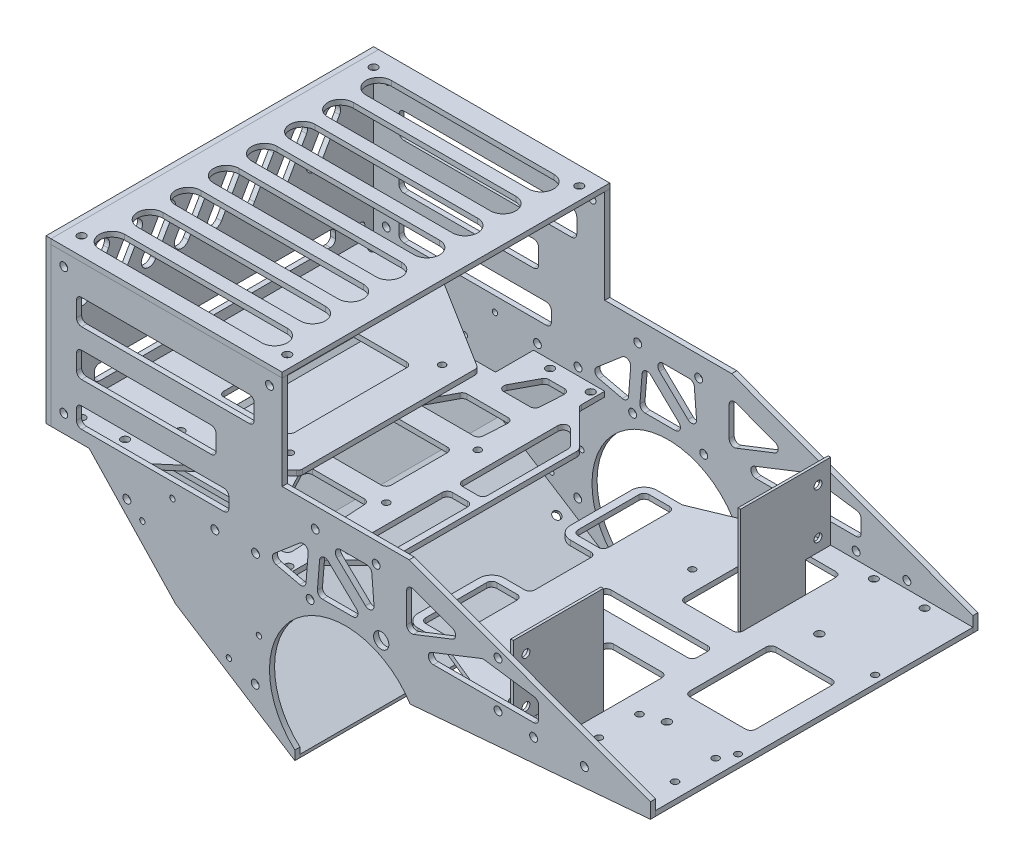
SolidWorks part; units mm, degrees
material "Thornel Mat VMA"
ref_plane "前视基准面" through (0, 0, 0) normal (0, 0, 1) x (1, 0, 0)
ref_plane "上视基准面" through (0, 0, 0) normal (0, 1, 0) x (1, 0, 0)
ref_plane "右视基准面" through (0, 0, 0) normal (1, 0, 0) x (0, 0, -1)
sketch "草图1" plane through (0, 0, 0) normal (0, 0, 1) x (1, 0, 0)
  line L1 (-45, 65) -> (25, 65)
  line L2 (25, 65) -> (120, 30)
  line L3 (120, 30) -> (120, 24)
  line L4 (120, 24) -> (41.8272, 24) construction
  line L5 (0, 32) -> (0, 57) construction
  line L6 (-12, 57) -> (12, 57) construction
  line L9 (29.8272, 3.2154) -> (41.8272, 24) construction
  line L15 (-18, 24) -> (-45, 24)
  line L17 (-45, 24) -> (-45, 65)
  line L18 (-14, 32) -> (14, 32) construction
  line L19 (60, 49) -> (90.2493, 37.8555) construction
  line L22 (120, 24) -> (120, 16) construction
  line L23 (120, 16) -> (25.3772, 16) construction
  line L24 (120, 24) -> (25.3772, 16)
  circle A2 centre (-12, 57) radius 1.55
  circle A3 centre (12, 57) radius 1.55
  circle A10 centre (90.2493, 37.8555) radius 1.55 construction
  circle A11 centre (60, 49) radius 1.55
  circle A13 centre (14, 32) radius 1.55
  circle A14 centre (-14, 32) radius 1.55
  arc A15 (-18, 24) -> (25.3772, 16) centre (0, 0) cw
  arc A16 (25.3772, 16) -> (29.8272, 3.2154) centre (0, 0) cw construction
  circle A17 centre (60, 31) radius 1.55
  point P27 (0, 57)
  dimension "D3" = 28
  dimension "D5" = 7
  dimension "D11" = 30
  dimension "D12" = 3.1
  dimension "D13" = 60
  dimension "D15" = 8
  dimension "D18" = 60
  dimension "D19" = 3.1
  dimension "D1" = 24
  dimension "D4" = 24
  dimension "D6" = 120
  dimension "D7" = 70
  dimension "D8" = 6
  dimension "D9" = 8
  dimension "D10" = 25
  dimension "D14" = 12
  dimension "D16" = 57
  dimension "D17" = 25
  dimension "D20" = 32
  dimension "D21" = 60
extrude "凸台-拉伸1" add sketch "草图1" along normal blind 2
sketch "草图2" plane through (0, 24, 0) normal (0, 1, 0) x (1, 0, 0)
  line L0 (120, -2) -> (120, 0) construction
  line L4 (120, 0) -> (120, 125)
  line L5 (120, 0) -> (21, 0)
  line L7 (45, 89.5) -> (117, 89.5) construction
  line L8 (45, 89.5) -> (45, 35.5) construction
  line L9 (45, 35.5) -> (117, 35.5) construction
  line L11 (45, 89.5) -> (117, 35.5) construction
  line L12 (45, 35.5) -> (117, 89.5) construction
  line L16 (120, 0) -> (25, 0) construction
  line L17 (21, 0) -> (21, 125) construction
  line L18 (21, 125) -> (120, 125)
  line L20 (117, 35.5) -> (117, 89.5) construction
  line L25 (84, 13.7) -> (114, 13.7) construction
  line L26 (84, 13.7) -> (84, 29.7) construction
  line L27 (84, 29.7) -> (114, 29.7) construction
  line L28 (114, 13.7) -> (114, 29.7) construction
  line L33 (81, 62.5) -> (76, 62.5) construction
  line L35 (21, 125) -> (21, 109.5)
  line L36 (21, 109.5) -> (11, 109.5)
  line L41 (6, 104.5) -> (6, 80.5)
  line L42 (11, 75.5) -> (21, 75.5)
  line L43 (21, 106.5) -> (11, 106.5)
  line L44 (9, 104.5) -> (9, 80.5)
  line L45 (11, 78.5) -> (21, 78.5)
  line L46 (21, 78.5) -> (21, 106.5)
  line L48 (21, 46.5) -> (21, 18.5)
  line L49 (21, 15.5) -> (11, 15.5)
  line L52 (21, 18.5) -> (11, 18.5)
  line L53 (34, 66.5) -> (76, 66.5)
  line L54 (34, 66.5) -> (34, 58.5)
  line L55 (34, 58.5) -> (76, 58.5)
  line L56 (76, 66.5) -> (76, 58.5)
  line L57 (6, 20.5) -> (6, 44.5)
  line L58 (9, 20.5) -> (9, 44.5)
  line L59 (11, 46.5) -> (21, 46.5)
  line L60 (11, 49.5) -> (21, 49.5)
  line L61 (21, 49.5) -> (21, 75.5)
  line L62 (21, 15.5) -> (21, 0)
  line L63 (92, 32.5) -> (92, 92.5) construction
  line L64 (120, 62.5) -> (21, 62.5) construction
  circle A0 centre (117, 89.5) radius 1.3
  circle A1 centre (117, 35.5) radius 1.3
  circle A2 centre (45, 35.5) radius 1.3
  circle A3 centre (45, 89.5) radius 1.3
  circle A7 centre (84, 13.7) radius 1.35
  circle A8 centre (84, 29.7) radius 1.35
  circle A9 centre (114, 13.7) radius 1.35
  circle A10 centre (114, 29.7) radius 1.35
  arc A11 (6, 80.5) -> (11, 75.5) centre (11, 80.5) ccw
  arc A12 (11, 109.5) -> (6, 104.5) centre (11, 104.5) ccw
  arc A13 (11, 106.5) -> (9, 104.5) centre (11, 104.5) ccw
  arc A14 (9, 80.5) -> (11, 78.5) centre (11, 80.5) ccw
  arc A15 (11, 15.5) -> (6, 20.5) centre (11, 20.5) cw
  arc A16 (11, 18.5) -> (9, 20.5) centre (11, 20.5) cw
  arc A17 (9, 44.5) -> (11, 46.5) centre (11, 44.5) cw
  arc A18 (6, 44.5) -> (11, 49.5) centre (11, 44.5) cw
  circle A19 centre (92, 92.5) radius 1.6
  circle A20 centre (92, 32.5) radius 1.6
  circle A21 centre (60, 5) radius 1.6
  circle A22 centre (60, 120) radius 1.6
  point P9 (81, 62.5)
  dimension "D4" = 2.6
  dimension "D10" = 30
  dimension "D15" = 28
  dimension "D17" = 5
  dimension "D19" = 42
  dimension "D20" = 12
  dimension "D21" = 28
  dimension "D22" = 3.2
  dimension "D23" = 3
  dimension "D24" = 3
  dimension "D8" = 2.7
  dimension "D13" = 5
  dimension "D25" = 5
  dimension "D2" = 54
  dimension "D3" = 72
  dimension "D5" = 24
  dimension "D6" = 3
  dimension "D7" = 0
  dimension "D9" = 16
  dimension "D11" = 5.8
  dimension "D12" = 6
  dimension "D14" = 3
  dimension "D16" = 13
  dimension "D18" = 8
  dimension "108" = 125
  dimension "D26" = 60
extrude "凸台-拉伸2" add sketch "草图2" along normal blind 2 separate body
extrude "凸台-拉伸3" add sketch "草图1<2>" against normal blind 2 from surface separate body starting at face at (70.5, 25, -125)
sketch "草图1<2>" plane through (0, 0, 0) normal (0, 0, 1) x (1, 0, 0) same geometry as "草图1"
sketch "草图16" plane through (0, 65, 0) normal (0, 1, 0) x (1, 0, 0)
  line L0 (-50, 30) -> (-85, 0)
  line L1 (-90, 125) -> (-116, 125)
  line L2 (-50, 100) -> (-50, 30)
  line L3 (-85, 0) -> (-116, 0)
  line L4 (-116, 125) -> (-116, 0)
  line L5 (-58, 94) -> (-98, 94) construction
  line L6 (-58, 94) -> (-58, 34) construction
  line L7 (-58, 34) -> (-98, 34) construction
  line L8 (-98, 94) -> (-98, 34) construction
  line L9 (-58, 94) -> (-98, 34) construction
  line L10 (-58, 34) -> (-98, 94) construction
  line L11 (25, 125) -> (-45, 125) construction
  line L12 (-50, 100) -> (-90, 125)
  line L13 (25, 0) -> (-45, 0) construction
  line L14 (-92, 88) -> (-92, 40)
  line L15 (-64, 40) -> (-92, 40)
  line L16 (-64, 88) -> (-64, 40)
  line L17 (-64, 88) -> (-92, 88)
  circle A0 centre (-98, 34) radius 1.35
  circle A1 centre (-58, 34) radius 1.35
  circle A2 centre (-58, 94) radius 1.35
  circle A3 centre (-98, 94) radius 1.35
  circle A4 centre (-111, 120) radius 1.55
  circle A5 centre (-111, 5) radius 1.55
  point P4 (-78, 64)
  dimension "D1" = 2.7
  dimension "D12" = 3.1
  dimension "D2" = 60
  dimension "D3" = 40
  dimension "D4" = 78
  dimension "D5" = 64
  dimension "D6" = 8
  dimension "D7" = 18
  dimension "D8" = 25
  dimension "D9" = 35
  dimension "D10" = 30
  dimension "D11" = 40
  dimension "D13" = 5
  dimension "D14" = 5
  dimension "D15" = 5
  dimension "D16" = 5
  dimension "D17" = 6
extrude "凸台-拉伸13" add sketch "草图16" along normal blind 2 from offset 25 separate body offset against normal yes
sketch "草图17" plane through (0, 24, 0) normal (0, -1, 0) x (1, 0, 0)
  line L0 (-45, -125) -> (-18, -125) construction
  line L1 (-66, -80) -> (-30, -80) construction
  line L2 (-66, -80) -> (-66, -44) construction
  line L3 (-66, -44) -> (-30, -44) construction
  line L4 (-30, -80) -> (-30, -44) construction
  line L5 (-25, -125) -> (-53, -125)
  line L6 (-25, -125) -> (-25, 0)
  line L7 (-25, 0) -> (-53, 0)
  line L8 (-90, -110) -> (-90, -15)
  line L10 (-45, 0) -> (-18, 0) construction
  line L11 (-25, -62.5) -> (-90, -62.5) construction
  line L13 (-53, 0) -> (-53, -15)
  line L14 (-53, -15) -> (-90, -15)
  line L15 (-53, -125) -> (-53, -110)
  line L16 (-53, -110) -> (-90, -110)
  line L17 (-53, -3) -> (-25, -3) construction
  line L18 (-61, -75) -> (-35, -75)
  line L19 (-35, -75) -> (-35, -49)
  line L20 (-61, -49) -> (-35, -49)
  line L21 (-61, -75) -> (-61, -49)
  line L22 (-43.5, -122) -> (-54.75, -101) construction
  line L25 (-54.75, -101) -> (-66, -80) construction
  line L26 (-43.5, -122) -> (-27.5, -122) construction
  line L27 (-54.75, -101) -> (-28.75, -101) construction
  line L28 (-27.5, -122) -> (-28.75, -101) construction
  line L29 (-28.75, -101) -> (-30, -80) construction
  line L30 (-41.105, -118) -> (-48.0693, -105)
  line L31 (-48.0693, -105) -> (-32.519, -105)
  line L32 (-31.7452, -118) -> (-32.519, -105)
  line L33 (-41.105, -118) -> (-31.7452, -118)
  line L34 (-52.355, -97) -> (-59.3193, -84)
  line L35 (-59.3193, -84) -> (-33.769, -84)
  line L36 (-32.9952, -97) -> (-33.769, -84)
  line L37 (-52.355, -97) -> (-32.9952, -97)
  line L38 (-52.355, -28) -> (-32.9952, -28)
  line L39 (-32.9952, -28) -> (-33.769, -41)
  line L40 (-59.3193, -41) -> (-33.769, -41)
  line L41 (-52.355, -28) -> (-59.3193, -41)
  line L42 (-41.105, -7) -> (-31.7452, -7)
  line L43 (-31.7452, -7) -> (-32.519, -20)
  line L44 (-48.0693, -20) -> (-32.519, -20)
  line L45 (-41.105, -7) -> (-48.0693, -20)
  circle A0 centre (-66, -80) radius 1.35
  circle A1 centre (-30, -80) radius 1.35
  circle A2 centre (-30, -44) radius 1.35
  circle A3 centre (-66, -44) radius 1.35
  circle A4 centre (-27.5, -3) radius 1.55
  circle A5 centre (-43.5, -3) radius 1.55
  circle A6 centre (-27.5, -122) radius 1.55
  circle A7 centre (-43.5, -122) radius 1.55
  dimension "D1" = 2.7
  dimension "D4" = 37
  dimension "D10" = 3.1
  dimension "D14" = 4
  dimension "D2" = 36
  dimension "D3" = 30
  dimension "D5" = 90
  dimension "D6" = 25
  dimension "D7" = 45
  dimension "D8" = 15
  dimension "D9" = 3
  dimension "D11" = 16
  dimension "D12" = 2.5
  dimension "D13" = 5
  dimension "D15" = 4
extrude "凸台-拉伸14" add sketch "草图17" along normal blind 2 from offset 10 separate body offset against normal yes
sketch "草图47" plane through (0, 34, 0) normal (0, 1, 0) x (1, 0, 0)
  line L0 (-25, 115) -> (-10, 100)
  line L1 (-10, 100) -> (-10, 25)
  line L2 (-10, 25) -> (-25, 10)
  line L3 (-25, 125) -> (-25, 0) construction
  line L4 (-25, 62.5) -> (-5.2813, 62.5) construction
  line L10 (-22.5, 108.9645) -> (-22.5, 16.0355)
  line L11 (-12.5, 26.0355) -> (-22.5, 16.0355)
  line L12 (-12.5, 98.9645) -> (-12.5, 26.0355)
  line L13 (-22.5, 108.9645) -> (-12.5, 98.9645)
  line L14 (-12.5, 84.5) -> (-22.5, 84.5) construction
  line L15 (-12.5, 80.5) -> (-22.5, 80.5) construction
  line L16 (-12.5, 60.5) -> (-22.5, 60.5)
  line L17 (-12.5, 64.5) -> (-22.5, 64.5)
  line L18 (-12.5, 44.5) -> (-22.5, 44.5) construction
  line L19 (-12.5, 40.5) -> (-22.5, 40.5) construction
  line L20 (-25, 115) -> (-25, 10) construction
  line L21 (-25, 115) -> (-25, 10)
  line L22 (-53, 125) -> (-25, 125) construction
  line M15 (-25, 0) -> (-25, 125)
  dimension "D1" = 15
  dimension "D2" = 45
  dimension "D3" = 2
  dimension "D5" = 4
  dimension "D6" = 18
  dimension "D7" = 10
  dimension "D4" = 2.5
extrude "凸台-拉伸27" add sketch "草图47" against normal up to surface (2 mm away) contours L12 L17 L10 L16 | L2 L1 L0 L10 L13 L12 L11 M15 region at (-18.25, 34, -106.75) region at (-17.5, 34, -62.5) up to face at (-29.05, 32, -122)
sketch "草图18" plane through (0, 0, -127) normal (0, 0, -1) x (-1, 0, 0)
  line L0 (45, 40) -> (101, 40) construction
  line L1 (45, 65) -> (45, 24) construction
  line L2 (101, 40) -> (67, 4)
  line L3 (67, 4) -> (20, -26)
  line L4 (20, -26) -> (20, -22.3607)
  line L5 (45, 24) -> (18, 24) construction
  line L6 (45, 40) -> (45, 24)
  line L7 (45, 24) -> (18, 24)
  line L8 (90, 42) -> (116, 42) construction
  line L13 (116, 40) -> (25, 40) construction
  line L14 (116, 40) -> (116, 102)
  line L15 (116, 102) -> (25, 102)
  line L16 (25, 40) -> (25, 102) construction
  line L17 (90, 40) -> (116, 40) construction
  line L18 (25, 102) -> (25, 65)
  line L19 (25, 65) -> (45, 65)
  line L20 (-25, 65) -> (45, 65) construction
  line L21 (45, 65) -> (45, 40)
  line L22 (101, 40) -> (116, 40)
  arc A0 (18, 24) -> (20, -22.3607) centre (0, 0) cw
  arc A1 (18, 24) -> (-25.3772, 16) centre (0, 0) ccw construction
  dimension "D1" = 56
  dimension "D2" = 22
  dimension "D3" = 91
  dimension "D4" = 50
  dimension "D5" = 25
  dimension "D6" = 36
  dimension "D7" = 60
  dimension "D8" = 25
extrude "凸台-拉伸15" add sketch "草图18" against normal up to surface (2 mm away) up to face at (61.55, 49, -125)
sketch "草图19" plane through (0, 0, -125) normal (0, 0, 1) x (1, 0, 0)
  line L0 (-20, -26) -> (-67, 4) construction
  line L1 (-67, 4) -> (-101, 40) construction
  line L2 (-20, -26) -> (-66.8959, 3.9335)
  line L3 (-67.0848, 4.0898) -> (-94.1338, 32.7299)
  line L4 (-19.462, -25.1571) -> (-66.3578, 4.7764)
  line L5 (-66.3578, 4.7764) -> (-93.4068, 33.4165)
  line L6 (-101, 40) -> (-100.273, 40.6866) construction
  line L7 (-20, -26) -> (-19.462, -25.1571)
  line L8 (-66.3578, 4.7764) -> (-67.0848, 4.0898)
  line L9 (-66.3578, 4.7764) -> (-66.8959, 3.9335)
  line L10 (-67, 4) -> (-101, 40) construction
  line L11 (-20, -26) -> (-67, 4) construction
  line L12 (-94.1338, 32.7299) -> (-93.4068, 33.4165)
  line L13 (-94.1338, 32.7299) -> (-101, 40) construction
  line L14 (-93.4068, 33.4165) -> (-100.273, 40.6866) construction
  line L15 (-66.3578, 4.7764) -> (-100.273, 40.6866) construction
  line M2 (-20, -26) -> (-20, -22.3607)
  line M11 (-101, 40) -> (-67, 4)
  line M12 (-67, 4) -> (-20, -26)
  dimension "D2" = 10
  dimension "D1" = 1
extrude "凸台-拉伸16" add sketch "草图19" along normal blind 125 separate body contours L8 L5 M11 | L4 L9 M12 M2 region at (-43.3137, -10.5269, -125) region at (-80.2458, 18.7532, -125)
sketch "草图38" plane through (0, 24, 0) normal (0, -1, 0) x (1, 0, 0)
  line L0 (104, -3) -> (84, -3) construction
  line L2 (120, 0) -> (120, -125) construction
  line L3 (42, -62.5) -> (120, -62.5) construction
  line L5 (120, 0) -> (25, 0) construction
  circle A0 centre (104, -3) radius 1.55
  circle A1 centre (84, -3) radius 1.55
  circle A2 centre (84, -122) radius 1.55
  circle A3 centre (104, -122) radius 1.55
  dimension "D2" = 3.1
  dimension "D1" = 20
  dimension "D3" = 3
  dimension "D4" = 16
extrude "切除-拉伸12" cut sketch "草图38" against normal up to surface (2 mm away) up to face at (55, 26, -62.5)
sketch "草图31" plane through (0, 0, -127) normal (0, 0, -1) x (-1, 0, 0)
  line L0 (39.3872, -13.6252) -> (35.621, -7.7247) construction
  line L1 (20, -24.8137) -> (66.3578, 4.7764) construction
  line L2 (88.3298, 28.0409) -> (86.1487, 30.1007) construction
  line L3 (66.3578, 4.7764) -> (93.4068, 33.4165) construction
  line L4 (66.3578, 4.7764) -> (67.0848, 4.0898) construction
  line L5 (20, -26) -> (67, 4) construction
  circle A0 centre (35.621, -7.7247) radius 1.55
  circle A1 centre (86.1487, 30.1007) radius 1.55
  dimension "D2" = 3.1
  dimension "D1" = 7
  dimension "D3" = 32
  dimension "D4" = 23
  dimension "D5" = 3
extrude "切除-拉伸7" cut sketch "草图31" against normal blind 2
sketch "草图62" plane through (-17.5812, -27.5439, 0) normal (-0.538, -0.8429, 0) x (0.8429, -0.538, 0)
  line L0 (-24.3195, -125) -> (-27.4195, -125) construction
  line L1 (-24.3195, -125) -> (-27.4195, -125) construction
  line L2 (-25.8695, -125) -> (-25.8695, -120) construction
  line L3 (-2.8695, -62.5) -> (-58.5044, -62.5) construction
  line L4 (-2.8695, 0) -> (-2.8695, -125) construction
  line L5 (-58.5044, 0) -> (-58.5044, -125) construction
  circle A0 centre (-25.8695, -120) radius 1.55
  circle A1 centre (-25.8695, -5) radius 1.55
  dimension "D1" = 5
  dimension "D2" = 3.1
extrude "切除-拉伸28" cut sketch "草图62" against normal through all
sketch "草图39" plane through (0, 0, -127) normal (0, 0, -1) x (-1, 0, 0)
  line L0 (-102.45, 26) -> (-105.55, 26) construction
  line L1 (-102.45, 26) -> (-105.55, 26) construction
  line L2 (-104, 26) -> (-104, 29) construction
  line L3 (-104, 29) -> (-74, 29) construction
  line L4 (-120, 26) -> (-21, 26) construction
  circle A0 centre (-74, 29) radius 1.55
  circle A1 centre (-94, 29) radius 1.55
  dimension "D1" = 20
  dimension "D3" = 3.1
  dimension "D2" = 10
  dimension "D4" = 3
extrude "切除-拉伸13" cut sketch "草图39" against normal through all
sketch "草图41" plane through (0, 0, 0) normal (0, 0, -1) x (-1, 0, 0)
  line L3 (-24, 56.8428) -> (-24, 39.3723)
  line L4 (-24, 34) -> (-76, 34)
  line L5 (-86.0018, 34) -> (-76, 37.6849) construction
  line L7 (-120, 30) -> (-25, 65) construction
  line L8 (-54, 45.7901) -> (-76, 42.6849)
  line L9 (-21, 26) -> (-120, 26) construction
  line L10 (-76, 42.6849) -> (-76, 37.6849)
  line L11 (-72.4303, 39) -> (-54, 45.7901) construction
  line L12 (-46.9445, 48.3895) -> (-24, 56.8428)
  line L13 (-76, 37.6849) -> (-72.4303, 39) construction
  line L14 (-24, 39.3723) -> (-46.9445, 48.3895)
  line L15 (-54, 45.7901) -> (-24, 34)
  line L16 (-54, 45.7901) -> (-46.9445, 48.3895) construction
  line L17 (-24, 39.3723) -> (-24, 34) construction
  line L18 (-76, 37.6849) -> (-76, 34)
  line L19 (-76, 34) -> (-86.0018, 34) construction
  circle A2 centre (-14, 32) radius 1.55 construction
  dimension "D2" = 30
  dimension "D5" = 8
  dimension "D6" = 10
  dimension "D7" = 8
  dimension "D8" = 5
  dimension "D9" = 5
  dimension "D10" = 22
extrude "切除-拉伸15" cut sketch "草图41" against normal through all both and the other way through all
sketch "草图48" plane through (0, 24, 0) normal (0, -1, 0) x (1, 0, 0)
  line L1 (53, -117) -> (76, -117)
  line L2 (53, -117) -> (53, -76.5)
  line L3 (53, -76.5) -> (76, -76.5)
  line L4 (76, -117) -> (76, -76.5)
  line L5 (53, -48.5) -> (76, -48.5)
  line L6 (53, -48.5) -> (53, -8)
  line L7 (53, -8) -> (76, -8)
  line L8 (76, -48.5) -> (76, -8)
  line L9 (21, 0) -> (120, 0) construction
  line L10 (34, -58.5) -> (76, -58.5) construction
  line L11 (76, -66.5) -> (34, -66.5) construction
  line L12 (25.3772, -125) -> (120, -125) construction
  line L13 (21, -125) -> (21, -109.5)
  line L14 (21, -109.5) -> (58.45, -125)
  line L15 (120, -125) -> (21, -125) construction
  line L16 (58.45, -125) -> (21, -125)
  line L17 (21, -15.5) -> (21, 0)
  line L18 (21, 0) -> (58.45, 0)
  line L19 (58.45, 0) -> (21, -15.5)
  line L20 (76, -58.5) -> (76, -66.5) construction
  line L21 (86, -79.5) -> (112, -79.5)
  line L22 (86, -79.5) -> (86, -45.5)
  line L23 (86, -45.5) -> (112, -45.5)
  line L24 (112, -79.5) -> (112, -45.5)
  line L25 (120, 0) -> (120, -125) construction
  circle A0 centre (45, -89.5) radius 1.3 construction
  circle A2 centre (45, -35.5) radius 1.3 construction
  circle A3 centre (84, -3) radius 1.55 construction
  circle A4 centre (84, -122) radius 1.55 construction
  circle A5 centre (117, -89.5) radius 1.3 construction
  circle A6 centre (117, -35.5) radius 1.3 construction
  dimension "D9" = 10
  dimension "D1" = 8
  dimension "D2" = 10
  dimension "D3" = 10
  dimension "D4" = 8
  dimension "D5" = 8
  dimension "D6" = 8
  dimension "D7" = 8
  dimension "D8" = 8
  dimension "D10" = 10
  dimension "D11" = 10
  dimension "D12" = 8
extrude "切除-拉伸19" cut sketch "草图48" against normal blind 10
fillet "圆角3" radius 2 24 edges at (21, 25, -18.5) (21, 25, -46.5) (21, 25, -106.5) (21, 25, -78.5) (76, 25, -58.5) (76, 25, -66.5) (34, 25, -66.5) (34, 25, -58.5) (21, 25, -75.5) (21, 25, -49.5) (21, 25, -109.5) (21, 25, -15.5) (76, 25, -76.5) (76, 25, -117) (53, 25, -117) (53, 25, -76.5) (76, 25, -8) (76, 25, -48.5) (53, 25, -8) (53, 25, -48.5) (112, 25, -45.5) (112, 25, -79.5) (86, 25, -79.5) (86, 25, -45.5)
fillet "圆角6" radius 2 10 edges at (-22.5, 33, -108.9645) (-12.5, 33, -98.9645) (-22.5, 33, -60.5) (-12.5, 33, -60.5) (-12.5, 33, -26.0355) (-12.5, 33, -64.5) (-22.5, 33, -64.5) (-22.5, 33, -16.0355) (-25, 33, -10) (-25, 33, -115)
extrude "凸台-拉伸29" add sketch "草图18<2>" against normal blind 2 from offset 127 offset against normal yes
sketch "草图18<2>" plane through (0, 0, -127) normal (0, 0, -1) x (-1, 0, 0) same geometry as "草图18"
sketch "草图51" plane through (0, 102, 0) normal (0, 1, 0) x (1, 0, 0)
  line L1 (-25, 127) -> (-116, 127)
  line L2 (-25, 127) -> (-25, -2)
  line L3 (-25, -2) -> (-116, -2)
  line L4 (-116, 127) -> (-116, -2)
extrude "凸台-拉伸30" add sketch "草图51" along normal blind 2 separate body
sketch "草图52" plane through (-116, 0, 0) normal (-1, 0, 0) x (0, 0, 1)
  line L1 (-127, 104) -> (2, 104)
  line L2 (-127, 104) -> (-127, 40)
  line L3 (-127, 40) -> (2, 40)
  line L4 (2, 104) -> (2, 40)
extrude "凸台-拉伸31" add sketch "草图52" along normal blind 2 separate body
sketch "草图53" plane through (0, 0, 0) normal (0, 0, 1) x (1, 0, 0)
  line L0 (-34.1664, 9.5634) -> (-46, -4) construction
  line L1 (-34.1664, 9.5634) -> (-68.2257, 39.2788) construction
  line L2 (-46, -4) -> (-80.0593, 25.7154) construction
  line L3 (-68.2257, 39.2788) -> (-80.0593, 25.7154) construction
  line L4 (-67, 4) -> (-101, 40) construction
  circle A0 centre (-68.2257, 39.2788) radius 1.05
  circle A1 centre (-80.0593, 25.7154) radius 1.05
  circle A2 centre (-46, -4) radius 1.05
  circle A3 centre (-34.1664, 9.5634) radius 1.05
  circle A4 centre (-86.1487, 30.1007) radius 1.55 construction
  circle A5 centre (-35.621, -7.7247) radius 1.55 construction
  circle A6 centre (-86.1487, 30.1007) radius 1.55
  circle A7 centre (-35.621, -7.7247) radius 1.55
  dimension "D3" = 2.1
  dimension "D1" = 45.2
  dimension "D2" = 18
  dimension "D4" = 5.533
  dimension "D5" = 46
  dimension "D6" = 4
extrude "切除-拉伸20" cut sketch "草图53" against normal through all both and the other way through all
fillet "圆角7" radius 2 2 edges at (-10, 33, -25) (-10, 33, -100)
sketch "草图55" plane through (0, 0, 2) normal (0, 0, 1) x (1, 0, 0)
  line L0 (-116, 40) -> (-116, 102) construction
  line L1 (-106, 90) -> (-36, 90)
  line L2 (-106, 90) -> (-106, 80)
  line L3 (-106, 80) -> (-36, 80)
  line L4 (-36, 90) -> (-36, 80)
  line L5 (-106, 72) -> (-51, 72)
  line L6 (-106, 72) -> (-106, 62)
  line L7 (-106, 62) -> (-51, 62)
  line L8 (-51, 72) -> (-51, 62)
  line L9 (-106, 53) -> (-46, 53)
  line L10 (-106, 53) -> (-106, 45)
  line L11 (-106, 45) -> (-46, 45)
  line L12 (-46, 53) -> (-46, 45)
  line L13 (-116, 102) -> (-25, 102) construction
  line L27 (-12, 57) -> (-14, 32) construction
  line L28 (-14, 32) -> (14, 32) construction
  line L29 (14, 32) -> (-12, 57) construction
  line L30 (7.7931, 34.5) -> (-9.9288, 51.5402)
  line L31 (-9.9288, 51.5402) -> (-11.292, 34.5)
  line L32 (-11.292, 34.5) -> (7.7931, 34.5)
  line L33 (-12, 57) -> (14, 32) construction
  line L34 (14, 32) -> (12, 57) construction
  line L35 (12, 57) -> (-12, 57) construction
  line L36 (10.1536, 55) -> (-7.0344, 55)
  line L37 (-7.0344, 55) -> (11.5859, 37.0958)
  line L38 (11.5859, 37.0958) -> (10.1536, 55)
  line L40 (-111, 97) -> (-30, 97) construction
  line L41 (-111, 97) -> (-111, 47) construction
  line L42 (-111, 47) -> (-30, 47) construction
  line L43 (-30, 97) -> (-30, 47) construction
  line L44 (-101, 40) -> (-116, 40) construction
  line L45 (-25, 102) -> (-25, 65) construction
  line L51 (-25, 32) -> (-25, 34) construction
  line L53 (-25, 34) -> (-53, 34) construction
  line L54 (-14, 32) -> (-35.5, 37) construction
  line L55 (-35.5, 37) -> (-12, 57) construction
  line L56 (-31.1815, 38.0491) -> (-14.3784, 52.3495)
  line L57 (-14.3784, 52.3495) -> (-15.8085, 34.4739)
  line L58 (-15.8085, 34.4739) -> (-31.1815, 38.0491)
  circle A0 centre (-111, 97) radius 1.55
  circle A3 centre (-111, 47) radius 1.55
  circle A5 centre (-30, 97) radius 1.55
  circle A6 centre (-35.5, 37) radius 1.55
  circle A7 centre (-51.5, 37) radius 1.55
  dimension "D13" = 5
  dimension "D16" = 3.1
  dimension "D21" = 16
  dimension "D1" = 10
  dimension "D2" = 10
  dimension "D3" = 12
  dimension "D4" = 10
  dimension "D5" = 8
  dimension "D6" = 8
  dimension "D7" = 55
  dimension "D8" = 9
  dimension "D9" = 70
  dimension "D10" = 60
  dimension "D11" = 2.5
  dimension "D12" = 2
  dimension "D14" = 5
  dimension "D15" = 7
  dimension "D17" = 5
  dimension "D18" = 2
  dimension "D22" = 10.5
  dimension "D23" = 3
extrude "切除-拉伸21" cut sketch "草图55" against normal through all
sketch "草图56" plane through (0, 104, 0) normal (0, 1, 0) x (1, 0, 0)
  line L0 (-39, 114) -> (-103, 114) construction
  line L1 (-39, 109) -> (-103, 109)
  line L2 (-39, 119) -> (-103, 119)
  line L3 (-25, 127) -> (-116, 127) construction
  line L4 (-116, -2) -> (-116, 127) construction
  line L5 (-39, 99) -> (-103, 99) construction
  line L6 (-39, 94) -> (-103, 94)
  line L7 (-39, 104) -> (-103, 104)
  line L8 (-39, 84) -> (-103, 84) construction
  line L9 (-39, 79) -> (-103, 79)
  line L10 (-39, 89) -> (-103, 89)
  line L11 (-39, 69) -> (-103, 69) construction
  line L12 (-39, 64) -> (-103, 64)
  line L13 (-39, 74) -> (-103, 74)
  line L14 (-39, 54) -> (-103, 54) construction
  line L15 (-39, 49) -> (-103, 49)
  line L16 (-39, 59) -> (-103, 59)
  line L17 (-39, 39) -> (-103, 39) construction
  line L18 (-39, 34) -> (-103, 34)
  line L19 (-39, 44) -> (-103, 44)
  line L20 (-39, 24) -> (-103, 24) construction
  line L21 (-39, 19) -> (-103, 19)
  line L22 (-39, 29) -> (-103, 29)
  line L23 (-39, 9) -> (-103, 9) construction
  line L24 (-39, 4) -> (-103, 4)
  line L25 (-39, 14) -> (-103, 14)
  line L26 (-116, -2) -> (-25, -2) construction
  line L27 (-30, 5) -> (-111, 5) construction
  line L28 (-30, 5) -> (-30, 120) construction
  line L29 (-30, 120) -> (-111, 120) construction
  line L30 (-111, 5) -> (-111, 120) construction
  line L31 (-25, -2) -> (-25, 127) construction
  line L32 (-116, 127) -> (-116, -2) construction
  arc A0 (-39, 109) -> (-39, 119) centre (-39, 114) ccw
  arc A1 (-103, 119) -> (-103, 109) centre (-103, 114) ccw
  arc A2 (-39, 94) -> (-39, 104) centre (-39, 99) ccw
  arc A3 (-103, 104) -> (-103, 94) centre (-103, 99) ccw
  arc A4 (-39, 79) -> (-39, 89) centre (-39, 84) ccw
  arc A5 (-103, 89) -> (-103, 79) centre (-103, 84) ccw
  arc A6 (-39, 64) -> (-39, 74) centre (-39, 69) ccw
  arc A7 (-103, 74) -> (-103, 64) centre (-103, 69) ccw
  arc A8 (-39, 49) -> (-39, 59) centre (-39, 54) ccw
  arc A9 (-103, 59) -> (-103, 49) centre (-103, 54) ccw
  arc A10 (-39, 34) -> (-39, 44) centre (-39, 39) ccw
  arc A11 (-103, 44) -> (-103, 34) centre (-103, 39) ccw
  arc A12 (-39, 19) -> (-39, 29) centre (-39, 24) ccw
  arc A13 (-103, 29) -> (-103, 19) centre (-103, 24) ccw
  arc A14 (-39, 4) -> (-39, 14) centre (-39, 9) ccw
  arc A15 (-103, 14) -> (-103, 4) centre (-103, 9) ccw
  circle A16 centre (-30, 5) radius 1.55
  circle A17 centre (-30, 120) radius 1.55
  circle A18 centre (-111, 5) radius 1.55
  circle A19 centre (-111, 120) radius 1.55
  point P2 (-71, 114)
  point P14 (-71, 99)
  point P21 (-71, 84)
  point P28 (-71, 69)
  point P35 (-71, 54)
  point P42 (-71, 39)
  point P49 (-71, 24)
  point P56 (-71, 9)
  dimension "D1" = 5
  dimension "D11" = 3.1
  dimension "D2" = 64
  dimension "D3" = 13
  dimension "D4" = 13
  dimension "D6" = 15
  dimension "D7" = 7
  dimension "D8" = 7
  dimension "D9" = 5
  dimension "D10" = 5
  dimension "D5" = 8
extrude "切除-拉伸22" cut sketch "草图56" against normal blind 10
sketch "草图57" plane through (-118, 0, 0) normal (-1, 0, 0) x (0, 0, 1)
  line L0 (-109, 91) -> (-101.5, 78.0096) construction
  line L1 (-106.4019, 92.5) -> (-98.9019, 79.5096)
  line L2 (-111.5981, 89.5) -> (-104.0981, 76.5096)
  line L3 (2, 104) -> (-127, 104) construction
  line L4 (-127, 104) -> (-127, 40) construction
  line L5 (-110, 52) -> (-15, 52)
  line L6 (-110, 52) -> (-110, 46)
  line L7 (-110, 46) -> (-15, 46)
  line L8 (-120, 97) -> (-120, 47)
  line L9 (-120, 47) -> (-5, 47)
  line L10 (-5, 47) -> (-5, 97)
  line L11 (-5, 97) -> (-120, 97)
  line L12 (-120, 97) -> (-120, 47) construction
  line L13 (-120, 47) -> (-5, 47) construction
  line L14 (-5, 47) -> (-5, 97) construction
  line L15 (-5, 97) -> (-120, 97) construction
  line L16 (-15, 52) -> (-15, 46)
  line L17 (-98.5981, 89.5) -> (-91.0981, 76.5096)
  line L18 (-93.4019, 92.5) -> (-85.9019, 79.5096)
  line L19 (-96, 91) -> (-88.5, 78.0096) construction
  line L20 (-85.5981, 89.5) -> (-78.0981, 76.5096)
  line L21 (-80.4019, 92.5) -> (-72.9019, 79.5096)
  line L22 (-83, 91) -> (-75.5, 78.0096) construction
  line L23 (-72.5981, 89.5) -> (-65.0981, 76.5096)
  line L24 (-67.4019, 92.5) -> (-59.9019, 79.5096)
  line L25 (-70, 91) -> (-62.5, 78.0096) construction
  line L26 (-59.5981, 89.5) -> (-52.0981, 76.5096)
  line L27 (-54.4019, 92.5) -> (-46.9019, 79.5096)
  line L28 (-57, 91) -> (-49.5, 78.0096) construction
  line L29 (-46.5981, 89.5) -> (-39.0981, 76.5096)
  line L30 (-41.4019, 92.5) -> (-33.9019, 79.5096)
  line L31 (-44, 91) -> (-36.5, 78.0096) construction
  line L32 (-33.5981, 89.5) -> (-26.0981, 76.5096)
  line L33 (-28.4019, 92.5) -> (-20.9019, 79.5096)
  line L34 (-31, 91) -> (-23.5, 78.0096) construction
  line L35 (-20.5981, 89.5) -> (-13.0981, 76.5096)
  line L36 (-15.4019, 92.5) -> (-7.9019, 79.5096)
  line L37 (-18, 91) -> (-10.5, 78.0096) construction
  line L38 (-111.5981, 89.5) -> (-98.5981, 89.5) construction
  circle A0 centre (-120, 97) radius 1.55
  circle A1 centre (-120, 47) radius 1.55
  circle A2 centre (-5, 47) radius 1.55
  circle A4 centre (-5, 97) radius 1.55
  arc A5 (-106.4019, 92.5) -> (-111.5981, 89.5) centre (-109, 91) ccw
  arc A6 (-104.0981, 76.5096) -> (-98.9019, 79.5096) centre (-101.5, 78.0096) ccw
  arc A7 (-93.4019, 92.5) -> (-98.5981, 89.5) centre (-96, 91) ccw
  arc A8 (-91.0981, 76.5096) -> (-85.9019, 79.5096) centre (-88.5, 78.0096) ccw
  arc A9 (-80.4019, 92.5) -> (-85.5981, 89.5) centre (-83, 91) ccw
  arc A10 (-78.0981, 76.5096) -> (-72.9019, 79.5096) centre (-75.5, 78.0096) ccw
  arc A11 (-67.4019, 92.5) -> (-72.5981, 89.5) centre (-70, 91) ccw
  arc A12 (-65.0981, 76.5096) -> (-59.9019, 79.5096) centre (-62.5, 78.0096) ccw
  arc A13 (-54.4019, 92.5) -> (-59.5981, 89.5) centre (-57, 91) ccw
  arc A14 (-52.0981, 76.5096) -> (-46.9019, 79.5096) centre (-49.5, 78.0096) ccw
  arc A15 (-41.4019, 92.5) -> (-46.5981, 89.5) centre (-44, 91) ccw
  arc A16 (-39.0981, 76.5096) -> (-33.9019, 79.5096) centre (-36.5, 78.0096) ccw
  arc A17 (-28.4019, 92.5) -> (-33.5981, 89.5) centre (-31, 91) ccw
  arc A18 (-26.0981, 76.5096) -> (-20.9019, 79.5096) centre (-23.5, 78.0096) ccw
  arc A19 (-15.4019, 92.5) -> (-20.5981, 89.5) centre (-18, 91) ccw
  arc A20 (-13.0981, 76.5096) -> (-7.9019, 79.5096) centre (-10.5, 78.0096) ccw
  point P14 (-105.25, 84.5048)
  point P27 (-92.25, 84.5048)
  point P34 (-79.25, 84.5048)
  point P41 (-66.25, 84.5048)
  point P48 (-53.25, 84.5048)
  point P55 (-40.25, 84.5048)
  point P62 (-27.25, 84.5048)
  point P69 (-14.25, 84.5048)
  dimension "D2" = 3.1
  dimension "D7" = 3
  dimension "D3" = 10
  dimension "D4" = 10
  dimension "D5" = 1
  dimension "D6" = 6
  dimension "D8" = 15
  dimension "D9" = 60
  dimension "D10" = 13
  dimension "D11" = 18
  dimension "D13" = 13
  dimension "D1" = 7
  dimension "D12" = 8
extrude "切除-拉伸23" cut sketch "草图57" against normal blind 10
sketch "草图58" plane through (0, 0, 0) normal (1, 0, 0) x (0, 0, -1)
  line L0 (125, 30) -> (125, -22.3607) construction
  line L1 (0, 56) -> (125, 56)
  line L2 (0, 56) -> (0, 14)
  line L3 (0, 14) -> (125, 14)
  line L4 (125, 56) -> (125, 14)
  line L5 (0, 24) -> (125, 24) construction
  line L6 (0, 30) -> (0, 65) construction
  dimension "D1" = 10
  dimension "D2" = 42
extrude "凸台-拉伸32" add sketch "草图58" along normal blind 1 from offset 63 separate body
sketch "草图59" plane through (64, 0, 0) normal (1, 0, 0) x (0, 0, -1)
  line L0 (62.5, 56) -> (62.5, 4.7764) construction
  line L1 (125, 56) -> (0, 56) construction
  line L2 (0, 4.7764) -> (125, 4.7764) construction
  line L3 (0, 56) -> (0, 14) construction
  line L4 (0, 14) -> (10, 14)
  line L5 (0, 14) -> (0, 26)
  line L6 (0, 26) -> (10, 26)
  line L7 (10, 14) -> (10, 26)
  line L8 (0, 26) -> (125, 26) construction
  line L10 (35.5, 14) -> (89.5, 14)
  line L11 (35.5, 14) -> (35.5, 64)
  line L12 (35.5, 64) -> (89.5, 64)
  line L13 (89.5, 14) -> (89.5, 64)
  line L14 (35.5, 14) -> (89.5, 64) construction
  line L15 (35.5, 64) -> (89.5, 14) construction
  line L16 (125, 26) -> (115, 26)
  line L17 (115, 14) -> (115, 26)
  line L18 (125, 14) -> (115, 14)
  line L19 (125, 14) -> (125, 26)
  line L20 (0, 14) -> (125, 14) construction
  line L21 (0, 24) -> (125, 24) construction
  circle A0 centre (5, 31) radius 1.55
  circle A1 centre (120, 31) radius 1.55
  circle A2 centre (5, 49) radius 1.55
  circle A3 centre (120, 49) radius 1.55
  point P17 (62.5, 39)
  dimension "D2" = 3.1
  dimension "D8" = 25
  dimension "D1" = 12
  dimension "D3" = 5
  dimension "D4" = 5
  dimension "D5" = 10
  dimension "D6" = 50
  dimension "D7" = 54
extrude "切除-拉伸24" cut sketch "草图59" against normal blind 2
fillet "圆角8" radius 2 28 edges at (24, 34, -126) (54, 45.7901, -126) (24, 56.8428, -126) (24, 39.3723, -126) (46.9445, 48.3895, -126) (10.1536, 55, -126) (-7.0344, 55, -126) (11.5859, 37.0958, -126) (7.7931, 34.5, -126) (-9.9288, 51.5402, -126) (-11.292, 34.5, -126) (-106, 45, -126) (-46, 45, -126) (-46, 53, -126) (-106, 53, -126) (-106, 62, -126) (-51, 62, -126) (-51, 72, -126) (-106, 72, -126) (-106, 80, -126) (-36, 80, -126) (-36, 90, -126) (-106, 90, -126) (76, 42.6849, -126) (76, 34, -126) (-14.3784, 52.3495, -126) (-31.1815, 38.0491, -126) (-15.8085, 34.4739, -126)
fillet "圆角9" radius 2 28 edges at (54, 45.7901, 1) (76, 42.6849, 1) (76, 34, 1) (24, 34, 1) (46.9445, 48.3895, 1) (24, 39.3723, 1) (24, 56.8428, 1) (11.5859, 37.0958, 1) (-7.0344, 55, 1) (10.1536, 55, 1) (-11.292, 34.5, 1) (-9.9288, 51.5402, 1) (7.7931, 34.5, 1) (-106, 53, 1) (-46, 53, 1) (-46, 45, 1) (-106, 72, 1) (-51, 72, 1) (-51, 62, 1) (-106, 62, 1) (-106, 90, 1) (-36, 90, 1) (-36, 80, 1) (-106, 80, 1) (-106, 45, 1) (-14.3784, 52.3495, 1) (-15.8085, 34.4739, 1) (-31.1815, 38.0491, 1)
fillet "圆角10" radius 2 4 edges at (-117, 52, -15) (-117, 46, -15) (-117, 52, -110) (-117, 46, -110)
sketch "草图60" plane through (0, 0, 0) normal (0, 1, 0) x (1, 0, 0)
  line L0 (-87, 105) -> (-87, 20) construction
  line L1 (-90, 15) -> (-90, 110) construction
  line L2 (-90, 62.5) -> (-10, 62.5) construction
  line L3 (-10, 99.1716) -> (-10, 25.8284) construction
  line L5 (-90, 110) -> (-53, 110) construction
  circle A0 centre (-95, 118.8564) radius 1.55
  circle A1 centre (-87, 105) radius 1.55
  circle A2 centre (-87, 20) radius 1.55
  circle A3 centre (-95, 6.1436) radius 1.55
  dimension "D2" = 3.1
  dimension "D1" = 3
  dimension "D3" = 16
  dimension "D4" = 5
  dimension "D5" = 8
extrude "切除-拉伸26" cut sketch "草图60" along normal through all
fillet "圆角11" radius 2 10 edges at (-92, 41, -40) (-64, 41, -40) (-116, 41, -125) (-90, 41, -125) (-50, 41, -100) (-50, 41, -30) (-85, 41, 0) (-116, 41, 0) (-64, 41, -88) (-92, 41, -88)
fillet "圆角12" radius 2 20 edges at (-41.105, 33, -7) (-48.0693, 33, -20) (-32.519, 33, -20) (-31.7452, 33, -7) (-52.355, 33, -28) (-59.3193, 33, -41) (-33.769, 33, -41) (-32.9952, 33, -28) (-33.769, 33, -84) (-59.3193, 33, -84) (-52.355, 33, -97) (-32.9952, 33, -97) (-32.519, 33, -105) (-48.0693, 33, -105) (-31.7452, 33, -118) (-35, 33, -75) (-35, 33, -49) (-61, 33, -49) (-61, 33, -75) (-41.105, 33, -118)
sketch "草图61" plane through (0, 0, 2) normal (0, 0, 1) x (1, 0, 0)
  circle A0 centre (14, 32) radius 3
  dimension "D1" = 6
extrude "切除-拉伸27" cut sketch "草图61" against normal blind 2
sketch "草图64" plane through (-33.416, -31.5595, 0) normal (-0.727, -0.6866, 0) x (0, 0, 1)
  line L0 (-62.5, 49.0354) -> (-62.5, 88.4295) construction
  line L1 (0, 49.0354) -> (-125, 49.0354) construction
  line L2 (0, 88.4295) -> (-125, 88.4295) construction
  line L3 (-127, 82.5854) -> (-127, 79.4854) construction
  line L4 (-127, 82.5854) -> (-127, 79.4854) construction
  line L5 (-127, 81.0354) -> (-120, 81.0354) construction
  circle A0 centre (-72.5, 54.0354) radius 1.55
  circle A1 centre (-52.5, 54.0354) radius 1.55
  circle A2 centre (-120, 81.0354) radius 1.55
  circle A3 centre (-5, 81.0354) radius 1.55
  dimension "D1" = 3.1
  dimension "D2" = 20
  dimension "D3" = 5
  dimension "D4" = 7
extrude "切除-拉伸29" cut sketch "草图64" against normal blind 10
sketch "草图65" plane through (-17.5812, -27.5439, 0) normal (-0.538, -0.8429, 0) x (0.8429, -0.538, 0)
  line L0 (-63.5974, -72.5) -> (-53.5044, -72.5) construction
  line L1 (-63.5974, -52.5) -> (-53.5044, -52.5) construction
  line L2 (-58.5044, 0) -> (-58.5044, -125) construction
  circle A0 centre (-53.5044, -72.5) radius 1.55
  circle A1 centre (-53.5044, -52.5) radius 1.55
  ellipse E0 centre (-63.5974, -52.5) end of major axis (-63.5974, -50.95) minor radius 1.5034 construction
  ellipse E1 centre (-63.5974, -72.5) end of major axis (-63.5974, -70.95) minor radius 1.5034 construction
  ellipse E2 centre (-63.5974, -52.5) end of major axis (-63.5974, -50.95) minor radius 1.5034 construction
  ellipse E3 centre (-63.5974, -72.5) end of major axis (-63.5974, -70.95) minor radius 1.5034 construction
  dimension "D2" = 3.1
  dimension "D1" = 5
extrude "切除-拉伸30" cut sketch "草图65" against normal blind 10
